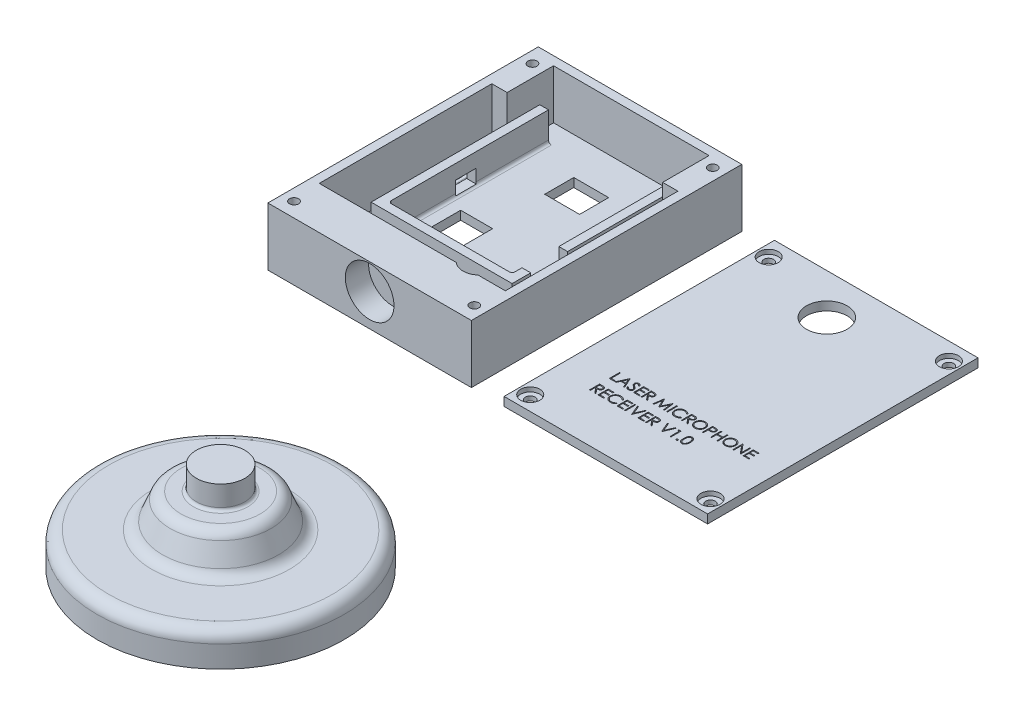
SolidWorks part; units mm, degrees
ref_plane "Front Plane" through (0, 0, 0) normal (0, 0, 1) x (1, 0, 0)
ref_plane "Top Plane" through (0, 0, 0) normal (0, 1, 0) x (1, 0, 0)
ref_plane "Right Plane" through (0, 0, 0) normal (1, 0, 0) x (0, 0, -1)
sketch "Sketch1" plane through (0, 0, 0) normal (0, 1, 0) x (1, 0, 0)
  line L1 (-32.5519, 43.6414) -> (37.4481, 43.6414)
  line L2 (-32.5519, 43.6414) -> (-32.5519, -49.3586)
  line L3 (-32.5519, -49.3586) -> (37.4481, -49.3586)
  line L4 (37.4481, 43.6414) -> (37.4481, -49.3586)
  dimension "D1" = 70
  dimension "D2" = 93
extrude "Boss-Extrude1" add sketch "Sketch1" along normal blind 20
sketch "Sketch4" plane through (0, 20, 0) normal (0, 1, 0) x (1, 0, 0)
  line L0 (37.4481, -49.3586) -> (37.4481, 43.6414) construction
  line L1 (-24.3019, 40.6414) -> (29.1981, 40.6414)
  line L2 (-24.3019, 40.6414) -> (-24.3019, -34.3586)
  line L3 (-24.3019, -34.3586) -> (29.1981, -34.3586)
  line L4 (29.1981, 40.6414) -> (29.1981, -34.3586)
  line L5 (-32.5519, 43.6414) -> (-32.5519, -49.3586) construction
  line L6 (-32.5519, -49.3586) -> (37.4481, -49.3586) construction
  line L7 (37.4481, 43.6414) -> (-32.5519, 43.6414) construction
  point P10 (2.4481, 40.6414)
  dimension "D1" = 8.25
  dimension "D2" = 8.25
  dimension "D3" = 15
  dimension "D4" = 3
extrude "Cut-Extrude1" cut sketch "Sketch4" against normal blind 17
sketch "Sketch5" plane through (0, 3, 0) normal (0, 1, 0) x (1, 0, 0)
  line L0 (-22.0416, 33.6414) -> (-19.0416, 33.6414)
  line L2 (-22.0416, 33.6414) -> (-22.0416, -24.3586)
  line L3 (-22.0416, -24.3586) -> (26.4584, -24.3586)
  line L4 (26.4584, 33.6414) -> (26.4584, -24.3586)
  line L6 (-19.0416, 33.6414) -> (-19.0416, -21.3586)
  line L7 (-19.0416, -21.3586) -> (23.4584, -21.3586)
  line L8 (23.4584, 33.6414) -> (23.4584, -21.3586)
  line L9 (23.4584, 33.6414) -> (26.4584, 33.6414)
  line L10 (29.1981, 40.6414) -> (-24.3019, 40.6414) construction
  dimension "D1" = 3
  dimension "D2" = 3
  dimension "D3" = 3
  dimension "D4" = 42.5
  dimension "D5" = 62
  dimension "D6" = 55
sketch "Sketch6" plane through (0, 20, 0) normal (0, 1, 0) x (1, 0, 0)
  line L0 (37.4481, -49.3586) -> (37.4481, 43.6414) construction
  line L1 (-29.5519, 24.678) -> (34.4481, 24.678)
  line L2 (-29.5519, 24.678) -> (-29.5519, -34.6843)
  line L3 (-29.5519, -34.6843) -> (34.4481, -34.6843)
  line L4 (34.4481, 24.678) -> (34.4481, -34.6843)
  line L5 (-32.5519, 43.6414) -> (-32.5519, -49.3586) construction
  dimension "D1" = 3
  dimension "D2" = 3
extrude "Cut-Extrude2" cut sketch "Sketch6" against normal blind 17
extrude "Boss-Extrude2" add sketch "Sketch5" along normal blind 10 contours L8 L7 L6 L0 L2 L3 L4 L9
sketch "Sketch8" plane through (23.4584, 0, 0) normal (-1, 0, 0) x (0, 0, 1)
  line L0 (-33.6414, 13) -> (-33.6414, 3) construction
  line L1 (-8.6414, 8.0464) -> (-1.6414, 8.0464)
  line L2 (-8.6414, 8.0464) -> (-8.6414, 3.4617)
  line L3 (-8.6414, 3.4617) -> (-1.6414, 3.4617)
  line L4 (-1.6414, 8.0464) -> (-1.6414, 3.4617)
  dimension "D1" = 25
  dimension "D2" = 7
extrude "Cut-Extrude3" cut sketch "Sketch8" against normal up to surface and the other way up to surface up to face at (26.4584, 8, -4.6414) other way up to face at (-22.0416, 8, -4.6414)
sketch "Sketch9" plane through (0, 3, 0) normal (0, 1, 0) x (1, 0, 0)
  line L0 (-27.1476, 9.1481) -> (-27.1476, 1.2091)
  line L1 (28.8524, 9.1481) -> (32.0018, 9.1481)
  line L2 (28.8524, 9.1481) -> (28.8524, 1.2091)
  line L3 (28.8524, 1.2091) -> (32.0018, 1.2091)
  line L4 (32.0018, 9.1481) -> (32.0018, 1.2091)
  line L5 (-27.1476, 9.1481) -> (-23.9982, 9.1481)
  line L6 (-23.9982, 9.1481) -> (-23.9982, 1.2091)
  line L7 (-27.1476, 1.2091) -> (-23.9982, 1.2091)
  dimension "D1" = 2
extrude "Cut-Extrude4" cut sketch "Sketch9" against normal up to surface (3 mm away) up to face at (2.4481, 0, 2.8586)
sketch "Sketch10" plane through (23.4584, 0, 0) normal (-1, 0, 0) x (0, 0, 1)
  line L1 (5.2978, 14.6212) -> (17.9569, 14.6212)
  line L2 (5.2978, 14.6212) -> (5.2978, 2.9802)
  line L3 (5.2978, 2.9802) -> (17.9569, 2.9802)
  line L4 (17.9569, 14.6212) -> (17.9569, 2.9802)
extrude "Cut-Extrude5" cut sketch "Sketch10" against normal up to surface (3 mm away) up to face at (26.4584, 5.7541, -5.1414)
sketch "Sketch11" plane through (0, 3, 0) normal (0, 1, 0) x (1, 0, 0)
  circle A0 centre (21.3153, -30.4969) radius 5.6
  circle A1 centre (30.6159, -30.951) radius 2.6
extrude "Cut-Extrude6" cut sketch "Sketch11" against normal blind 10 and the other way blind 19
sketch "Sketch12" plane through (0, 3, 0) normal (0, 1, 0) x (1, 0, 0)
  line L0 (34.4481, -34.6843) -> (34.4481, 24.678) construction
  line L1 (32.5825, -18.3636) -> (34.4481, -18.3636)
  line L2 (32.5825, -18.3636) -> (32.5825, -24.8085)
  line L3 (32.5825, -24.8085) -> (34.4481, -24.8085)
  line L4 (34.4481, -18.3636) -> (34.4481, -24.8085)
  line L6 (27.2362, -18.3636) -> (29.3601, -18.3636)
  line L7 (27.2362, -18.3636) -> (27.2362, -24.8085)
  line L8 (27.2362, -24.8085) -> (29.3601, -24.8085)
  line L9 (29.3601, -18.3636) -> (29.3601, -24.8085)
extrude "Cut-Extrude7" cut sketch "Sketch12" against normal up to surface (3 mm away) up to face at (21.3153, 0, 36.0969)
sketch "Sketch13" plane through (0, 3, 0) normal (0, 1, 0) x (1, 0, 0)
  line L0 (23.4584, 33.6414) -> (23.4584, -5.2978) construction
  line L1 (-4.5416, 27.8414) -> (7.4584, 27.8414)
  line L2 (-4.5416, 27.8414) -> (-4.5416, 17.8414)
  line L3 (-4.5416, 17.8414) -> (7.4584, 17.8414)
  line L4 (7.4584, 27.8414) -> (7.4584, 17.8414)
  line L5 (-14.2416, -1.3586) -> (-3.2416, -1.3586)
  line L6 (-14.2416, -1.3586) -> (-14.2416, -11.3586)
  line L7 (-14.2416, -11.3586) -> (-3.2416, -11.3586)
  line L8 (-3.2416, -1.3586) -> (-3.2416, -11.3586)
  line L9 (23.4584, 33.6414) -> (26.4584, 33.6414) construction
  line L10 (-19.0416, 33.6414) -> (-19.0416, -21.3586) construction
  line L11 (-19.0416, -21.3586) -> (23.4584, -21.3586) construction
  line L12 (-19.0416, 33.6414) -> (-19.0416, -21.3586) construction
  point P12 (24.9584, 33.6414)
  dimension "D1" = 16
  dimension "D2" = 5.8
  dimension "D3" = 10
  dimension "D4" = 14.5
  dimension "D5" = 10
  dimension "D6" = 10
  dimension "D7" = 4.8
  dimension "D8" = 11
extrude "Cut-Extrude8" cut sketch "Sketch13" against normal up to surface (3 mm away) up to face at (33.5153, 0, 21.5861)
sketch "Sketch14" plane through (0, 0, 49.3586) normal (0, 0, 1) x (1, 0, 0)
  line L0 (-32.5519, 0) -> (37.4481, 0) construction
  circle A0 centre (2.4481, 11.1338) radius 8.3636
  point P6 (2.4481, 0)
  dimension "D1" = 16.7273
extrude "Cut-Extrude9" cut sketch "Sketch14" against normal blind 8
sketch "Sketch15" plane through (0, 20, 0) normal (0, 1, 0) x (1, 0, 0)
  line L0 (37.4481, -49.3586) -> (37.4481, 43.6414) construction
  line L1 (37.4481, 43.6414) -> (-32.5519, 43.6414) construction
  line L2 (-32.5519, 43.6414) -> (-32.5519, -49.3586) construction
  circle A0 centre (33.4481, 37.6414) radius 1.55
  circle A1 centre (-28.5519, 37.6414) radius 1.55
  circle A2 centre (33.4481, -44.3586) radius 1.55
  circle A3 centre (-28.5519, -44.3586) radius 1.55
  dimension "D1" = 2
  dimension "D2" = 4
  dimension "D3" = 6
  dimension "D4" = 4
  dimension "D5" = 2
extrude "Cut-Extrude10" cut sketch "Sketch15" against normal up to surface (20 mm away) up to face at (1.4584, 0, -22.8414)
sketch "Sketch16" plane through (0, 0, 0) normal (0, -1, 0) x (1, 0, 0)
  line L1 (29.9319, 46.351) -> (29.9646, 42.3096)
  line L2 (29.9646, 42.3096) -> (33.4808, 40.3173)
  line L3 (33.4808, 40.3173) -> (36.9643, 42.3663)
  line L4 (36.9643, 42.3663) -> (36.9316, 46.4076)
  line L5 (36.9316, 46.4076) -> (33.4154, 48.3999)
  line L6 (33.4154, 48.3999) -> (29.9319, 46.351)
  line L7 (-28.5519, 48.4001) -> (-32.0519, 46.3793)
  line L8 (-32.0519, 46.3793) -> (-32.0519, 42.3379)
  line L9 (-32.0519, 42.3379) -> (-28.5519, 40.3172)
  line L10 (-28.5519, 40.3172) -> (-25.0519, 42.3379)
  line L11 (-25.0519, 42.3379) -> (-25.0519, 46.3793)
  line L12 (-25.0519, 46.3793) -> (-28.5519, 48.4001)
  line L13 (33.4481, -33.5999) -> (29.9481, -35.6207)
  line L14 (29.9481, -35.6207) -> (29.9481, -39.6621)
  line L15 (29.9481, -39.6621) -> (33.4481, -41.6828)
  line L16 (33.4481, -41.6828) -> (36.9481, -39.6621)
  line L17 (36.9481, -39.6621) -> (36.9481, -35.6207)
  line L18 (36.9481, -35.6207) -> (33.4481, -33.5999)
  line L19 (-28.5519, -33.5999) -> (-32.0519, -35.6207)
  line L20 (-32.0519, -35.6207) -> (-32.0519, -39.6621)
  line L21 (-32.0519, -39.6621) -> (-28.5519, -41.6828)
  line L22 (-28.5519, -41.6828) -> (-25.0519, -39.6621)
  line L23 (-25.0519, -39.6621) -> (-25.0519, -35.6207)
  line L24 (-25.0519, -35.6207) -> (-28.5519, -33.5999)
  circle A0 centre (33.4481, 44.3586) radius 3.5 construction
  circle A1 centre (-28.5519, 44.3586) radius 3.5 construction
  circle A2 centre (33.4481, -37.6414) radius 3.5 construction
  circle A3 centre (-28.5519, -37.6414) radius 3.5 construction
  dimension "D1" = 3.5
  dimension "D2" = 3.5
  dimension "D3" = 3.5
  dimension "D4" = 3.5
extrude "Cut-Extrude11" cut sketch "Sketch16" against normal blind 16
sketch "Sketch17" plane through (0, 0, 0) normal (0, 1, 0) x (1, 0, 0)
  line L0 (37.4481, 43.6414) -> (-32.5519, 43.6414) construction
  line L1 (48.6881, 43.6414) -> (118.6881, 43.6414)
  line L2 (48.6881, 43.6414) -> (48.6881, -49.3586)
  line L3 (48.6881, -49.3586) -> (118.6881, -49.3586)
  line L4 (118.6881, 43.6414) -> (118.6881, -49.3586)
  line L5 (-32.5519, -49.3586) -> (37.4481, -49.3586) construction
  dimension "D1" = 70
extrude "Boss-Extrude3" add sketch "Sketch17" along normal blind 3 separate body
sketch "Sketch18" plane through (0, 3, 0) normal (0, 1, 0) x (1, 0, 0)
  line L0 (118.6881, 43.6414) -> (48.6881, 43.6414) construction
  line L1 (48.6881, 43.6414) -> (48.6881, -49.3586) construction
  circle A0 centre (52.6881, 37.6414) radius 1.65
  circle A1 centre (114.6881, 37.6414) radius 1.65
  circle A2 centre (114.6881, -44.3586) radius 1.65
  circle A3 centre (52.6881, -44.3586) radius 1.65
  dimension "D1" = 6
  dimension "D2" = 4
  dimension "D3" = 2
  dimension "D4" = 2
extrude "Cut-Extrude12" cut sketch "Sketch18" against normal blind 12
sketch "Sketch19" plane through (0, 3, 0) normal (0, 1, 0) x (1, 0, 0)
  line L0 (23.4584, 33.6414) -> (68.0423, 33.6414)
  line L2 (118.6881, -49.3586) -> (118.6881, 43.6414) construction
  circle A0 centre (80.6881, 29.6414) radius 7
  dimension "D2" = 14
  dimension "D1" = 38
  dimension "D3" = 4
extrude "Cut-Extrude13" cut sketch "Sketch19" against normal blind 12 contours A0
other "Save Bodies1"
other "Save Bodies2"
sketch "Sketch21" plane through (0, 0, 0) normal (0, 1, 0) x (1, 0, 0)
  circle A0 centre (48.1487, -146.3095) radius 42.5
extrude "Boss-Extrude4" add sketch "Sketch21" along normal blind 11.5 separate body
sketch "Sketch22" plane through (0, 11.5, 0) normal (0, 1, 0) x (1, 0, 0)
  circle A0 centre (48.1487, -146.3095) radius 20.9629
  circle A1 centre (48.1487, -146.3095) radius 42.5 construction
extrude "Boss-Extrude5" add sketch "Sketch22" along normal blind 11.5 draft 22
sketch "Sketch23" plane through (0, 23, 0) normal (0, 1, 0) x (1, 0, 0)
  circle A0 centre (48.1487, -146.3095) radius 8.355
  dimension "D1" = 16.71
extrude "Boss-Extrude6" add sketch "Sketch23" along normal blind 8
fillet "Fillet5" radius 4 3 edges at (48.1487, 11.5, 188.8095) (48.1487, 11.5, 167.2724) (48.1487, 23, 162.6261)
fillet "Fillet6" radius 1 1 edges at (48.1487, 23, 154.6645) type face fillet first side face at (48.1487, 31, 154.6645) second side face at (48.1487, 23, 159.9281)
fillet "Fillet7" radius 1 1 edges at (2.2084, 3, 24.3586) type face fillet first side face at (2.2084, 8, 24.3586) second side face at (1.4584, 3, -22.8414)
fillet "Fillet8" radius 1 1 edges at (2.2084, 3, 21.3586) type face fillet first side face at (1.4584, 3, -22.8414) second side face at (2.2084, 8, 21.3586)
fillet "Fillet9" radius 1 4 edges at (-19.0416, 3.2929, 21.0657) (-19.0416, 8.5, 21.3586) (-19.0416, 3, -6.6414) (-19.0416, 3.4617, -5.1414)
fillet "Fillet10" radius 1 3 edges at (-22.0416, 3.2929, 24.6515) (-22.0416, 3, -4.1414) (-22.0416, 3.4617, -5.1414)
fillet "Fillet11" radius 1 2 edges at (23.4584, 3, -14.1718) (23.4584, 3.4617, -5.1414)
fillet "Fillet12" radius 1 2 edges at (26.4584, 3, -14.1718) (26.4584, 3.4617, -5.1414)
fillet "Fillet13" radius 1 3 edges at (23.4584, 3, 19.1578) (23.4584, 3.2929, 21.0657) (23.4584, 8.5, 21.3586)
fillet "Fillet14" radius 1 3 edges at (26.4584, 3, 21.6578) (27.2362, 3, 21.5861) (26.4584, 3.2929, 24.6515)
other "Save Bodies3"
other "Save Bodies4"
sketch "Sketch26" plane through (0, 3, 0) normal (0, 1, 0) x (1, 0, 0)
  circle A0 centre (52.6881, 37.6414) radius 3.2916
  circle A1 centre (114.6881, 37.6414) radius 3.2916
  circle A2 centre (114.6881, -44.3586) radius 3.2916
  circle A3 centre (52.6881, -44.3586) radius 3.2916
  dimension "D1" = 2
  dimension "D2" = 2
extrude "Cut-Extrude15" cut sketch "Sketch26" against normal blind 1.5
sketch "Sketch27" plane through (0, 3, 0) normal (0, 1, 0) x (1, 0, 0)
  text T0 "LASER MICROPHONE\r\nRECEIVER V1.0"
extrude "Cut-Extrude16" cut sketch "Sketch27" against normal blind 1.5
other "Save Bodies5"
